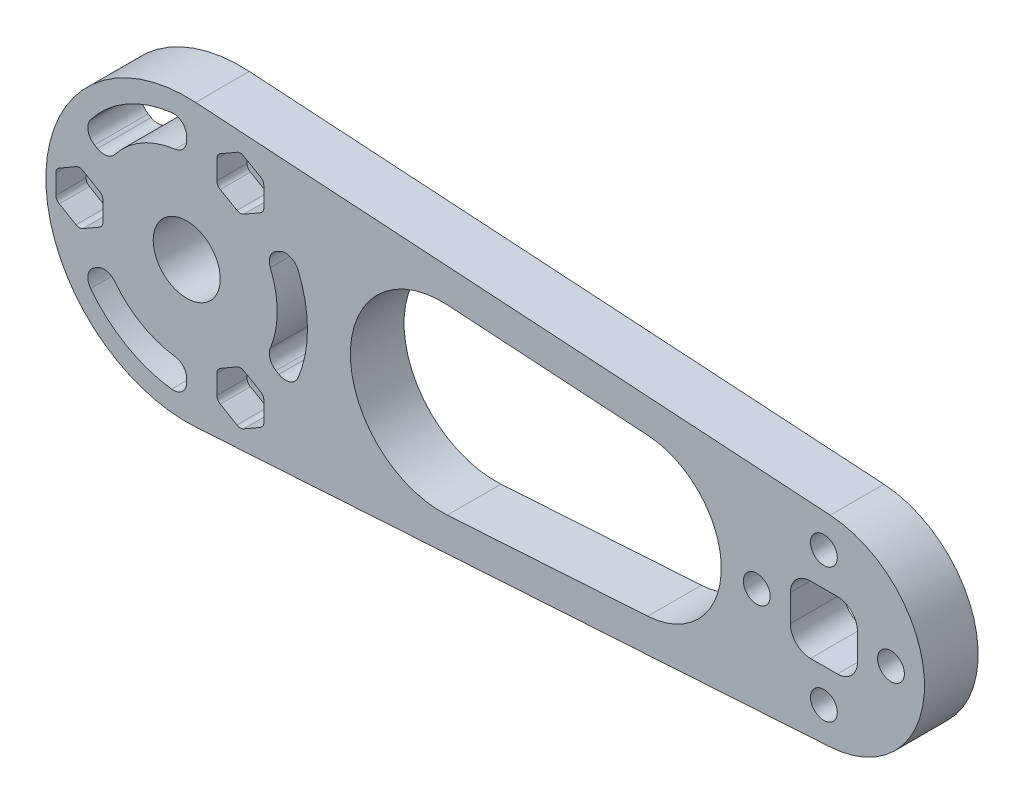
SolidWorks part; units mm, degrees
note: The reader was unsure of these and kept them because the rebuilt part matched: shared geometry of "草图1<3>".
material "7075-T6 (SN)"
ref_plane "前视基准面" through (0, 0, 0) normal (0, 0, 1) x (1, 0, 0)
ref_plane "上视基准面" through (0, 0, 0) normal (0, 1, 0) x (1, 0, 0)
ref_plane "右视基准面" through (0, 0, 0) normal (1, 0, 0) x (0, 0, -1)
sketch "草图1" plane through (0, 0, 0) normal (0, 0, 1) x (1, 0, 0)
  circle A0 centre (0, 0) radius 16 construction
  circle A1 centre (-16, 0) radius 2
  circle A2 centre (8, 13.8564) radius 2
  circle A3 centre (8, -13.8564) radius 2
  circle A4 centre (0, 0) radius 21
  circle A5 centre (0, 0) radius 20
  point P11 (0, 0)
  dimension "D1" = 32
  dimension "D2" = 4
  dimension "D4" = 42
  dimension "D5" = 40
  dimension "D3" = 3
extrude "凸台-拉伸1" add sketch "草图1" along normal blind 8 contours A4 A5 | A5 A3 A2 A1
extrude "凸台-拉伸2" add sketch "草图1<3>" against normal blind 7 contours A5 A3 A2 A1
sketch "草图1<3>" plane through (0, 0, 0) normal (0, 0, 1) x (1, 0, 0) same geometry as "草图1"
sketch "草图3" plane through (0, 0, -7) normal (0, 0, -1) x (-1, 0, 0)
  circle A0 centre (0, 0) radius 5
  dimension "D1" = 10
sketch "草图7" plane through (0, 0, -7) normal (0, 0, -1) x (-1, 0, 0)
  line L0 (-6.5, 11.2583) -> (-8, 13.8564) construction
  line L1 (0, 13.5) -> (0, 18)
  line L2 (11.6913, -6.75) -> (15.5885, -9)
  line L3 (11.6913, 6.75) -> (15.5885, 9)
  line L4 (0, -13.5) -> (0, -18)
  line L5 (-11.6913, -6.75) -> (-15.5885, -9)
  line L6 (-11.6913, 6.75) -> (-15.5885, 9)
  line L7 (-8, 13.8564) -> (0, 0) construction
  arc A0 (15.5885, 9) -> (0, 18) centre (0, 0) ccw
  arc A1 (11.6913, 6.75) -> (0, 13.5) centre (0, 0) ccw
  arc A2 (0, -18) -> (15.5885, -9) centre (0, 0) ccw
  arc A3 (0, -13.5) -> (11.6913, -6.75) centre (0, 0) ccw
  arc A4 (-15.5885, 9) -> (-15.5885, -9) centre (0, 0) ccw
  arc A5 (-11.6913, 6.75) -> (-11.6913, -6.75) centre (0, 0) ccw
  point P21 (0, 0)
  dimension "D1" = 36
  dimension "D2" = 27
  dimension "D4" = 3
extrude "切除-拉伸10" cut sketch "草图3" against normal blind 25
extrude "切除-拉伸11" cut sketch "草图7" against normal blind 25
fillet "圆角8" radius 2 12 edges at (0, 13.5, 0.5) (0, 18, 0.5) (0, -18, 0.5) (0, -13.5, 0.5) (-11.6913, -6.75, 0.5) (-15.5885, -9, 0.5) (15.5885, 9, 0.5) (11.6913, 6.75, 0.5) (11.6913, -6.75, 0.5) (15.5885, -9, 0.5) (-11.6913, 6.75, 0.5) (-15.5885, 9, 0.5)
sketch "草图12" plane through (0, 0, 8) normal (0, 0, 1) x (1, 0, 0)
  line L0 (0, 0) -> (95, 0) construction
  line L1 (1.3263, 20.9581) -> (95.9474, 14.9701)
  line L2 (1.05, -20.9737) -> (95.75, -14.9812)
  arc A0 (95.75, -14.9812) -> (95.9474, 14.9701) centre (95, 0) ccw
  circle A1 centre (0, 0) radius 21 construction
  arc A2 (1.05, -20.9737) -> (1.3263, 20.9581) centre (0, 0) ccw
  dimension "D2" = 30
  dimension "D1" = 95
extrude "凸台-拉伸4" add sketch "草图12" against normal blind 8
sketch "草图13" plane through (0, 0, 8) normal (0, 0, 1) x (1, 0, 0)
  line L2 (0, 0) -> (95, 0) construction
  line L3 (0, 0) -> (38, 0) construction
  line L6 (95, 0) -> (68, 0) construction
  line L7 (38.8588, 13.5712) -> (68.7391, 11.6805)
  line L11 (1.2864, -15.9488) -> (95.4342, -9.9912)
  line L12 (38.8588, -13.5712) -> (68.7391, -11.6805)
  circle A15 centre (95, 0) radius 15 construction
  arc A17 (84.6647, -0.0532) -> (84.6647, -0.0254) centre (73, -0.0448) ccw
  arc A18 (38.8588, 13.5712) -> (38.8588, -13.5712) centre (38, 0) ccw
  arc A19 (68.7391, -11.6805) -> (68.7391, 11.6805) centre (68, 0) ccw
  dimension "D2" = 5
  dimension "D3" = 38
  dimension "D4" = 27
sketch "草图14" plane through (0, 0, 8) normal (0, 0, 1) x (1, 0, 0)
  circle A0 centre (95, 0) radius 10 construction
  circle A1 centre (95, 10) radius 2
  circle A2 centre (105, 0) radius 2
  circle A3 centre (95, -10) radius 2
  circle A4 centre (85, 0) radius 2
  point P14 (95, 0)
  dimension "D1" = 20
  dimension "D2" = 4
  dimension "D3" = 4
extrude "切除-拉伸13" cut sketch "草图14" against normal blind 8
sketch "草图15" plane through (0, 0, 8) normal (0, 0, 1) x (1, 0, 0)
  line L1 (90, -5) -> (100, -5)
  line L2 (90, -5) -> (90, 5)
  line L3 (90, 5) -> (100, 5)
  line L4 (100, -5) -> (100, 5)
  line L5 (90, -5) -> (100, 5) construction
  line L6 (90, 5) -> (100, -5) construction
  point P0 (95, 0)
  dimension "D1" = 10
extrude "切除-拉伸14" cut sketch "草图15" against normal blind 20
sketch "草图16" plane through (0, 0, 0) normal (0, 0, -1) x (-1, 0, 0)
  circle A0 centre (0, 0) radius 20
extrude "切除-拉伸15" cut sketch "草图16" along normal blind 26
sketch "草图17" plane through (0, 0, 8) normal (0, 0, 1) x (1, 0, 0)
  line L0 (4.5, -11.8357) -> (4.5, -15.8771)
  line L1 (8, 9.815) -> (11.5, 11.8357)
  line L2 (11.5, 11.8357) -> (11.5, 15.8771)
  line L3 (11.5, 15.8771) -> (8, 17.8979)
  line L4 (8, 17.8979) -> (4.5, 15.8771)
  line L5 (4.5, 15.8771) -> (4.5, 11.8357)
  line L6 (4.5, 11.8357) -> (8, 9.815)
  line L7 (4.5, -15.8771) -> (8, -17.8979)
  line L8 (8, -17.8979) -> (11.5, -15.8771)
  line L9 (11.5, -15.8771) -> (11.5, -11.8357)
  line L10 (11.5, -11.8357) -> (8, -9.815)
  line L11 (8, -9.815) -> (4.5, -11.8357)
  line L12 (-12.5, 2.0207) -> (-16, 4.0415)
  line L13 (-16, 4.0415) -> (-19.5, 2.0207)
  line L14 (-19.5, 2.0207) -> (-19.5, -2.0207)
  line L15 (-19.5, -2.0207) -> (-16, -4.0415)
  line L16 (-16, -4.0415) -> (-12.5, -2.0207)
  line L17 (-12.5, -2.0207) -> (-12.5, 2.0207)
  circle A0 centre (8, 13.8564) radius 3.5 construction
  circle A1 centre (8, -13.8564) radius 3.5 construction
  circle A2 centre (-16, 0) radius 3.5 construction
  point P28 (0, 0)
  dimension "D1" = 3
extrude "切除-拉伸16" cut sketch "草图17" against normal blind 4.5
extrude "切除-拉伸17" cut sketch "草图13" against normal blind 10 contours L12 A19 L7 A18
fillet "圆角9" radius 1 18 edges at (-12.5, 2.0207, 5.75) (-16, 4.0415, 5.75) (-19.5, 2.0207, 5.75) (-19.5, -2.0207, 5.75) (-16, -4.0415, 5.75) (-12.5, -2.0207, 5.75) (4.5, -11.8357, 5.75) (4.5, -15.8771, 5.75) (8, -17.8979, 5.75) (11.5, -15.8771, 5.75) (11.5, -11.8357, 5.75) (8, -9.815, 5.75) (8, 9.815, 5.75) (11.5, 11.8357, 5.75) (4.5, 15.8771, 5.75) (4.5, 11.8357, 5.75) (11.5, 15.8771, 5.75) (8, 17.8979, 5.75)
fillet "圆角10" radius 3 4 edges at (90, -5, 4) (100, -5, 4) (100, 5, 4) (90, 5, 4)
